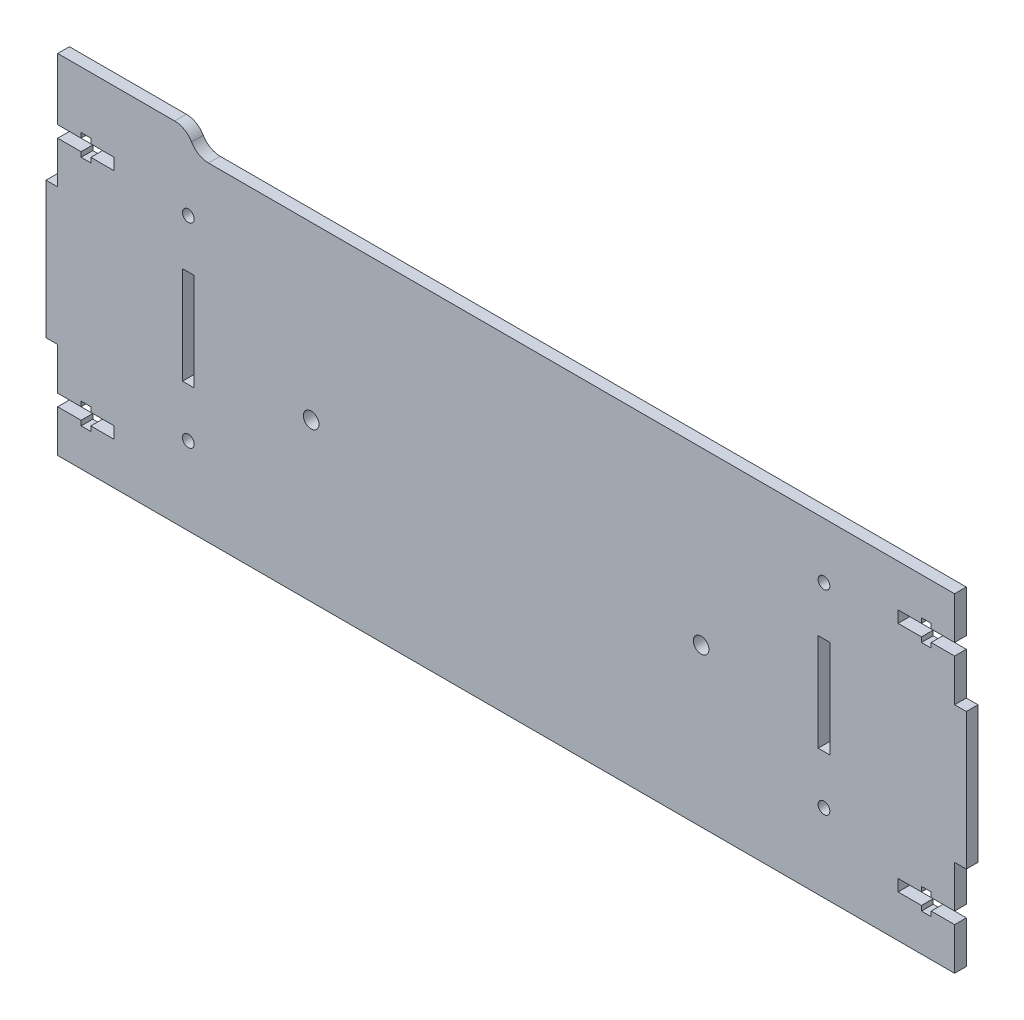
SolidWorks part; units mm, degrees
ref_plane "Спереди" through (0, 0, 0) normal (0, 0, 1) x (1, 0, 0)
ref_plane "Сверху" through (0, 0, 0) normal (0, 1, 0) x (1, 0, 0)
ref_plane "Справа" through (0, 0, 0) normal (1, 0, 0) x (0, 0, -1)
sketch "Эскиз1" plane through (0, 0, 0) normal (0, 0, 1) x (1, 0, 0)
  line L1 (0, 0) -> (230, 0)
  line L2 (0, 0) -> (0, 84.29)
  line L3 (0, 84.29) -> (230, 84.29)
  line L4 (230, 0) -> (230, 84.29)
  dimension "D1" = 84.29
  dimension "D2" = 230
extrude "Бобышка-Вытянуть1" add sketch "Эскиз1" along normal blind 3
sketch "Эскиз3" plane through (230, 0, 0) normal (1, 0, 0) x (0, 0, -1)
  line L0 (-3, 0) -> (-3, 84.29) construction
  line L1 (-3, 24.645) -> (0, 24.645)
  line L2 (-3, 24.645) -> (-3, 59.645)
  line L3 (-3, 59.645) -> (0, 59.645)
  line L4 (0, 24.645) -> (0, 59.645)
  line L5 (0, 0) -> (0, 84.29) construction
  point P9 (0, 42.145)
  point P10 (0, 42.145)
  dimension "D1" = 35
extrude "Бобышка-Вытянуть2" add sketch "Эскиз3" along normal blind 3 and the other way blind 233
sketch "Эскиз2" plane through (0, 0, 3) normal (0, 0, 1) x (1, 0, 0)
  line L0 (0, 0) -> (230, 0) construction
  circle A0 centre (65, 40.4) radius 2
  circle A1 centre (165, 40.4) radius 2
  point P8 (115, 0)
  dimension "D1" = 4
  dimension "D2" = 100
  dimension "D3" = 50
  dimension "D4" = 40.4
extrude "Вырез-Вытянуть1" cut sketch "Эскиз2" against normal blind 3
sketch "Эскиз5" plane through (0, 0, 3) normal (0, 0, 1) x (1, 0, 0)
  line L0 (0, 0) -> (230, 0) construction
  circle A0 centre (33.5, 70) radius 1.5
  circle A1 centre (33.5, 20) radius 1.5
  circle A2 centre (196.5, 20) radius 1.5
  circle A3 centre (196.5, 70) radius 1.5
  point P13 (115, 0)
  dimension "D1" = 3
  dimension "D2" = 20
  dimension "D3" = 163
  dimension "D4" = 81.5
  dimension "D5" = 50
extrude "Вырез-Вытянуть2" cut sketch "Эскиз5" against normal blind 3
sketch "Эскиз6" plane through (0, 0, 3) normal (0, 0, 1) x (1, 0, 0)
  line L0 (0, 0) -> (230, 0) construction
  line L1 (32, 32.5) -> (35, 32.5)
  line L2 (32, 32.5) -> (32, 57.5)
  line L3 (32, 57.5) -> (35, 57.5)
  line L4 (35, 32.5) -> (35, 57.5)
  line L5 (32, 32.5) -> (35, 57.5) construction
  line L6 (32, 57.5) -> (35, 32.5) construction
  line L7 (195, 32.5) -> (198, 32.5)
  line L8 (195, 32.5) -> (195, 57.5)
  line L9 (195, 57.5) -> (198, 57.5)
  line L10 (198, 32.5) -> (198, 57.5)
  line L11 (195, 32.5) -> (198, 57.5) construction
  line L12 (195, 57.5) -> (198, 32.5) construction
  circle A0 centre (33.5, 20) radius 1.5 construction
  point P0 (33.5, 45)
  point P5 (196.5, 45)
  point P16 (115, 0)
  dimension "D1" = 3
  dimension "D2" = 25
  dimension "D3" = 163
  dimension "D4" = 25
  dimension "D5" = 81.5
extrude "Вырез-Вытянуть3" cut sketch "Эскиз6" against normal blind 3
sketch "Эскиз7" plane through (0, 0, 3) normal (0, 0, 1) x (1, 0, 0)
  line L0 (0, 73.4675) -> (6, 73.4675)
  line L1 (6, 73.4675) -> (6, 74.7175)
  line L2 (6, 74.7175) -> (8.5, 74.7175)
  line L3 (8.5, 74.7175) -> (8.5, 73.4675)
  line L4 (8.5, 73.4675) -> (14.5, 73.4675)
  line L5 (14.5, 73.4675) -> (14.5, 70.4675)
  line L6 (14.5, 70.4675) -> (8.5, 70.4675)
  line L7 (8.5, 70.4675) -> (8.5, 69.2175)
  line L8 (8.5, 69.2175) -> (6, 69.2175)
  line L9 (6, 69.2175) -> (6, 70.4675)
  line L10 (6, 70.4675) -> (0, 70.4675)
  line L11 (0, 70.4675) -> (0, 73.4675)
  line L12 (0, 84.29) -> (0, 59.645) construction
  line L13 (-3, 42.145) -> (5.379, 42.145) construction
  line L14 (-3, 59.645) -> (-3, 24.645) construction
  line L15 (115, 84.29) -> (115, 45.3561) construction
  line L16 (230, 84.29) -> (0, 84.29) construction
  line L17 (0, 13.8225) -> (0, 10.8225)
  line L18 (6, 13.8225) -> (0, 13.8225)
  line L19 (6, 15.0725) -> (6, 13.8225)
  line L20 (8.5, 15.0725) -> (6, 15.0725)
  line L21 (8.5, 13.8225) -> (8.5, 15.0725)
  line L22 (14.5, 13.8225) -> (8.5, 13.8225)
  line L23 (14.5, 10.8225) -> (14.5, 13.8225)
  line L24 (8.5, 10.8225) -> (14.5, 10.8225)
  line L25 (8.5, 9.5725) -> (8.5, 10.8225)
  line L26 (6, 9.5725) -> (8.5, 9.5725)
  line L27 (6, 10.8225) -> (6, 9.5725)
  line L28 (0, 10.8225) -> (6, 10.8225)
  line L29 (230, 10.8225) -> (224, 10.8225)
  line L30 (224, 10.8225) -> (224, 9.5725)
  line L31 (224, 9.5725) -> (221.5, 9.5725)
  line L32 (221.5, 9.5725) -> (221.5, 10.8225)
  line L33 (221.5, 10.8225) -> (215.5, 10.8225)
  line L34 (215.5, 10.8225) -> (215.5, 13.8225)
  line L35 (215.5, 13.8225) -> (221.5, 13.8225)
  line L36 (221.5, 13.8225) -> (221.5, 15.0725)
  line L37 (221.5, 15.0725) -> (224, 15.0725)
  line L38 (224, 15.0725) -> (224, 13.8225)
  line L39 (224, 13.8225) -> (230, 13.8225)
  line L40 (230, 13.8225) -> (230, 10.8225)
  line L41 (230, 70.4675) -> (230, 73.4675)
  line L42 (224, 70.4675) -> (230, 70.4675)
  line L43 (224, 69.2175) -> (224, 70.4675)
  line L44 (221.5, 69.2175) -> (224, 69.2175)
  line L45 (221.5, 70.4675) -> (221.5, 69.2175)
  line L46 (215.5, 70.4675) -> (221.5, 70.4675)
  line L47 (215.5, 73.4675) -> (215.5, 70.4675)
  line L48 (221.5, 73.4675) -> (215.5, 73.4675)
  line L49 (221.5, 74.7175) -> (221.5, 73.4675)
  line L50 (224, 74.7175) -> (221.5, 74.7175)
  line L51 (224, 73.4675) -> (224, 74.7175)
  line L52 (230, 73.4675) -> (224, 73.4675)
  point P16 (0, 71.9675)
  point P17 (0, 71.9675)
  dimension "D1" = 6
  dimension "D2" = 3
  dimension "D3" = 5.5
  dimension "D4" = 2.5
  dimension "D5" = 12.3225
extrude "Вырез-Вытянуть4" cut sketch "Эскиз7" against normal blind 3
sketch "Эскиз8" plane through (0, 84.29, 0) normal (0, 1, 0) x (1, 0, 0)
  line L0 (230, 0) -> (0, 0) construction
  line L1 (0, -3) -> (35, -3)
  line L2 (0, -3) -> (0, 0)
  line L3 (0, 0) -> (35, 0)
  line L4 (35, -3) -> (35, 0)
  dimension "D1" = 35
extrude "Бобышка-Вытянуть3" add sketch "Эскиз8" along normal blind 5
fillet "Скругление1" radius 5 1 edges at (35, 89.29, 1.5)
fillet "Скругление2" radius 5 1 edges at (35, 84.29, 1.5)
